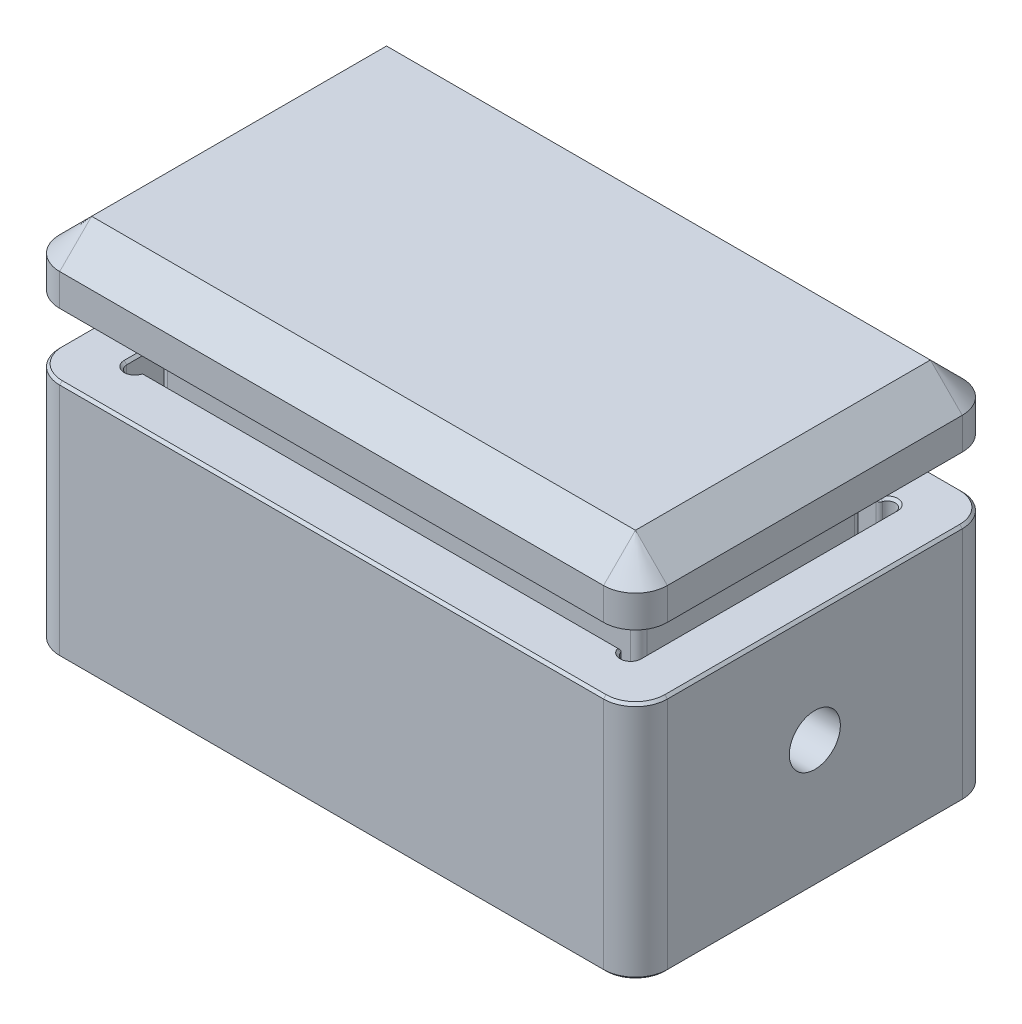
SolidWorks part; units mm, degrees
material "Nylon 101"
ref_plane "Front Plane" through (0, 0, 0) normal (0, 0, 1) x (1, 0, 0)
ref_plane "Top Plane" through (0, 0, 0) normal (0, 1, 0) x (1, 0, 0)
ref_plane "Right Plane" through (0, 0, 0) normal (1, 0, 0) x (0, 0, -1)
sketch "Sketch1" plane through (0, 0, 0) normal (0, 1, 0) x (1, 0, 0)
  line L0 (0, 12.7635) -> (50.927, 12.7635) construction
  line L1 (1.6, 0) -> (49.327, 0)
  line L2 (0, 0) -> (0, 25.527)
  line L3 (1.6, 25.527) -> (49.327, 25.527)
  line L4 (50.927, 0) -> (50.927, 25.527)
  line L5 (0, 25.527) -> (1.6, 25.527) construction
  line L6 (49.327, 25.527) -> (50.927, 25.527) construction
  line L8 (-4.7625, 30.607) -> (55.6895, 30.607)
  line L9 (-4.7625, 30.607) -> (-4.7625, -5.08)
  line L10 (-4.7625, -5.08) -> (55.6895, -5.08)
  line L11 (55.6895, 30.607) -> (55.6895, -5.08)
  arc A0 (0, 0) -> (1.6, 0) centre (0.8, 0) ccw
  arc A1 (50.927, 0) -> (49.327, 0) centre (50.127, 0) cw
  arc A2 (0, 25.527) -> (1.6, 25.527) centre (0.8, 25.527) cw
  arc A3 (50.927, 25.527) -> (49.327, 25.527) centre (50.127, 25.527) ccw
  dimension "D3" = 0.8
  dimension "D1" = 25.527
  dimension "D2" = 50.927
  dimension "D4" = 5.08
  dimension "D5" = 4.7625
  dimension "D6" = 5.08
  dimension "D7" = 4.7625
extrude "Boss-Extrude1" add sketch "Sketch1" along normal blind 23.8125
fillet "Fillet1" radius 3.175 4 edges at (-4.7625, 11.9062, -30.607) (55.6895, 11.9062, -30.607) (55.6895, 11.9062, 5.08) (-4.7625, 11.9062, 5.08)
fillet "Fillet2" radius 0.4 4 edges at (49.327, 11.9062, 0) (49.327, 11.9062, -25.527) (1.6, 11.9062, -25.527) (1.6, 11.9062, 0)
ref_plane "Plane1" through (0, 30.1625, 0) normal (0, 1, 0) x (1, 0, 0)
sketch "Sketch2" plane through (0, 30.1625, 0) normal (0, 1, 0) x (1, 0, 0)
  line L0 (50.927, 0) -> (50.927, 25.527) construction
  line L1 (0, 0) -> (50.927, 0) construction
  line L2 (0, 0) -> (0, 25.527) construction
  line L3 (0, 25.527) -> (50.927, 25.527) construction
  line L4 (52.5145, 30.607) -> (-1.5875, 30.607)
  line L5 (-4.7625, 27.432) -> (-4.7625, -1.905)
  line L6 (-1.5875, -5.08) -> (52.5145, -5.08)
  line L7 (55.6895, -1.905) -> (55.6895, 27.432)
  line L8 (52.5145, 30.607) -> (-1.5875, 30.607)
  line L9 (-4.7625, 27.432) -> (-4.7625, -1.905)
  line L10 (-1.5875, -5.08) -> (52.5145, -5.08)
  line L11 (55.6895, -1.905) -> (55.6895, 27.432)
  line L12 (50.927, 0) -> (50.927, 25.527) construction
  line L13 (48.9956, 25.527) -> (1.9314, 25.527) construction
  line L14 (1.6256, 23.9014) -> (49.3014, 23.9014)
  line L15 (49.3014, 1.6256) -> (49.3014, 23.9014)
  line L16 (1.6256, 1.6256) -> (49.3014, 1.6256)
  line L17 (1.6256, 1.6256) -> (1.6256, 23.9014)
  arc A4 (-1.5875, 30.607) -> (-4.7625, 27.432) centre (-1.5875, 27.432) ccw
  arc A5 (-4.7625, -1.905) -> (-1.5875, -5.08) centre (-1.5875, -1.905) ccw
  arc A6 (52.5145, -5.08) -> (55.6895, -1.905) centre (52.5145, -1.905) ccw
  arc A7 (55.6895, 27.432) -> (52.5145, 30.607) centre (52.5145, 27.432) ccw
  arc A8 (-1.5875, 30.607) -> (-4.7625, 27.432) centre (-1.5875, 27.432) ccw
  arc A9 (-4.7625, -1.905) -> (-1.5875, -5.08) centre (-1.5875, -1.905) ccw
  arc A10 (52.5145, -5.08) -> (55.6895, -1.905) centre (52.5145, -1.905) ccw
  arc A11 (55.6895, 27.432) -> (52.5145, 30.607) centre (52.5145, 27.432) ccw
  dimension "D1" = 0
  dimension "D2" = 1.6256
extrude "Boss-Extrude2" add sketch "Sketch2" along normal blind 6.35 separate body contours L17 L16 L15 L14 | L11 A11 L8 A8 L9 A9 L10 A10 L16 L17 L14 L15 region at (54.2632, 30.1625, -29.1807) region at (25.4635, 30.1625, -12.7635)
extrude "Boss-Extrude3" add sketch "Sketch2<4>" against normal up to surface (30.1625 mm away) contours L17 L16 L15 L14 region at (25.4635, 30.1625, -12.7635) up to face at (25.4635, 0, -12.7635)
sketch "Sketch2<4>" plane through (0, 30.1625, 0) normal (0, 1, 0) x (1, 0, 0) same geometry as "Sketch2"
chamfer "Chamfer1" distance 3.175 angle 45 8 edges at (54.7596, 36.5125, 4.1501) (25.4635, 36.5125, 5.08) (-3.8326, 36.5125, 4.1501) (-4.7625, 36.5125, -12.7635) (-3.8326, 36.5125, -29.6771) (25.4635, 36.5125, -30.607) (54.7596, 36.5125, -29.6771) (55.6895, 36.5125, -12.7635)
chamfer "Chamfer2" distance 4.7625 angle 45 4 edges at (1.6256, 0, -12.7635) (25.4635, 0, -1.6256) (49.3014, 0, -12.7635) (25.4635, 0, -23.9014)
chamfer "Chamfer3" distance 0.254 angle 45 40 edges at (50.927, 23.8125, -12.7635) (50.2623, 23.8125, -26.3155) (49.2266, 23.8125, -25.6004) (25.4635, 23.8125, -25.527) (1.7004, 23.8125, -25.6004) (0.6647, 23.8125, -26.3155) (0, 23.8125, -12.7635) (0.6647, 23.8125, 0.7885) (1.7004, 23.8125, 0.0734) (25.4635, 23.8125, 0) (49.2266, 23.8125, 0.0734) (50.2623, 23.8125, 0.7885) (54.7596, 23.8125, -29.6771) (55.6895, 23.8125, -12.7635) (54.7596, 23.8125, 4.1501) (25.4635, 23.8125, 5.08) (-3.8326, 23.8125, 4.1501) (-4.7625, 23.8125, -12.7635) (-3.8326, 23.8125, -29.6771) (25.4635, 23.8125, -30.607) (1.7004, 0, 0.0734) (0.6647, 0, 0.7885) (0, 0, -12.7635) (0.6647, 0, -26.3155) (1.7004, 0, -25.6004) (25.4635, 0, -25.527) (49.2266, 0, -25.6004) (50.2623, 0, -26.3155) (50.927, 0, -12.7635) (50.2623, 0, 0.7885) (49.2266, 0, 0.0734) (25.4635, 0, 0) (-3.8326, 0, 4.1501) (25.4635, 0, 5.08) (54.7596, 0, 4.1501) (55.6895, 0, -12.7635) (54.7596, 0, -29.6771) (25.4635, 0, -30.607) (-3.8326, 0, -29.6771) (-4.7625, 0, -12.7635)
fillet "Fillet3" radius 0.8106 4 edges at (1.6256, 17.4625, -23.9014) (49.3014, 17.4625, -1.6256) (1.6256, 17.4625, -1.6256) (49.3014, 17.4625, -23.9014)
sketch "Sketch3" plane through (55.6895, 0, 0) normal (1, 0, 0) x (0, 0, -1)
  line L2 (27.432, 23.5585) -> (-1.905, 23.5585) construction
  line L3 (12.7635, 0.254) -> (12.7635, 23.5585) construction
  line L4 (-1.905, 0.254) -> (27.432, 0.254) construction
  line L5 (-1.905, 30.1625) -> (27.432, 30.1625) construction
  circle A0 centre (12.7635, 12.7) radius 2.54
  point P8 (12.7635, 17.2085)
  dimension "D3" = 5.08
  dimension "D1" = 17.4625
extrude "Cut-Extrude1" cut sketch "Sketch3" against normal through all
equation "\"D3@Sketch1\"=0.4mm *2"
